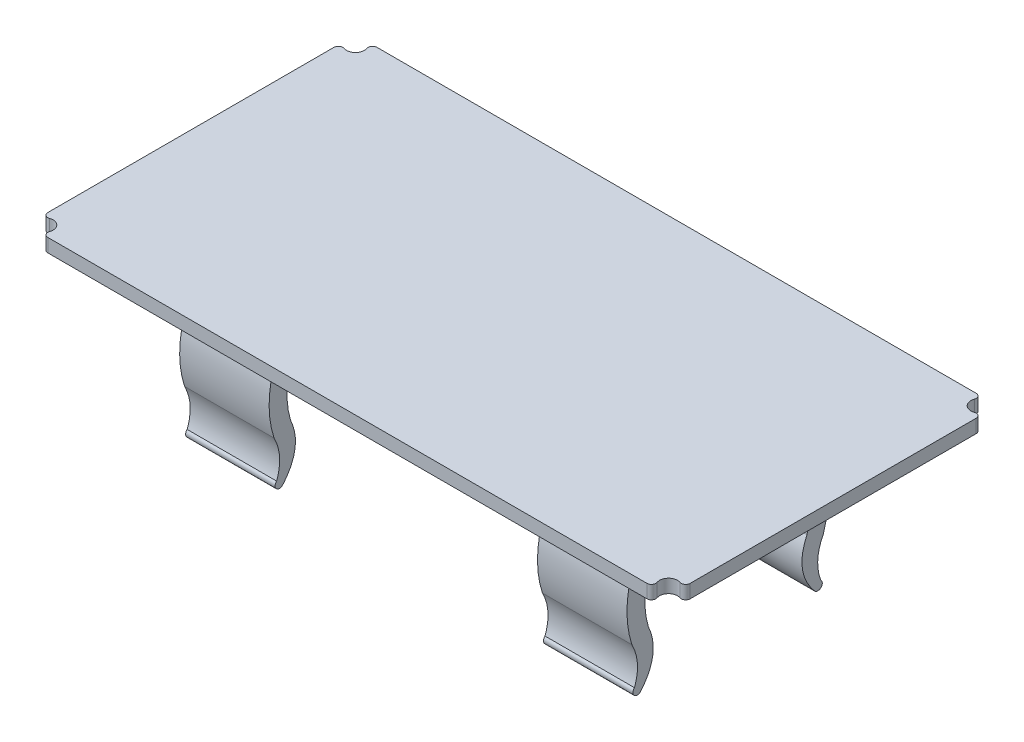
SolidWorks part; units mm, degrees
ref_plane "Front Plane" through (0, 0, 0) normal (0, 0, 1) x (1, 0, 0)
ref_plane "Top Plane" through (0, 0, 0) normal (0, 1, 0) x (1, 0, 0)
ref_plane "Right Plane" through (0, 0, 0) normal (1, 0, 0) x (0, 0, -1)
sketch "Sketch1" plane through (0, 0, 0) normal (0, 1, 0) x (1, 0, 0)
  line L1 (2.4142, 0) -> (69.3858, 0)
  line L2 (0, 2.4142) -> (0, 34.3858)
  line L3 (2.4142, 36.8) -> (69.3858, 36.8)
  line L4 (71.8, 2.4142) -> (71.8, 34.3858)
  arc A0 (0.6667, 34.8572) -> (1.9428, 36.1333) centre (1, 35.8) ccw
  arc A1 (1.9428, 0.6667) -> (0.6667, 1.9428) centre (1, 1) ccw
  arc A2 (71.1333, 1.9428) -> (69.8572, 0.6667) centre (70.8, 1) ccw
  arc A3 (69.8572, 36.1333) -> (71.1333, 34.8572) centre (70.8, 35.8) ccw
  arc A4 (69.8572, 36.1333) -> (69.3858, 36.8) centre (69.3858, 36.3) ccw
  arc A5 (71.8, 34.3858) -> (71.1333, 34.8572) centre (71.3, 34.3858) ccw
  arc A6 (71.1333, 1.9428) -> (71.8, 2.4142) centre (71.3, 2.4142) ccw
  arc A7 (69.8572, 0.6667) -> (69.3858, 0) centre (69.3858, 0.5) cw
  arc A8 (2.4142, 0) -> (1.9428, 0.6667) centre (2.4142, 0.5) cw
  arc A9 (0, 2.4142) -> (0.6667, 1.9428) centre (0.5, 2.4142) ccw
  arc A10 (2.4142, 36.8) -> (1.9428, 36.1333) centre (2.4142, 36.3) ccw
  arc A11 (0, 34.3858) -> (0.6667, 34.8572) centre (0.5, 34.3858) cw
  dimension "D3" = 1
  dimension "D7" = 1
  dimension "D2" = 0.5
  dimension "D4" = 1
  dimension "D5" = 1
  dimension "D6" = 1
  dimension "D8" = 1
  dimension "D9" = 1
  dimension "D10" = 1
extrude "Boss-Extrude1" add sketch "Sketch1" along normal blind 1.5
sketch "Sketch2" plane through (0, 0, 0) normal (0, -1, 0) x (1, 0, 0)
  line L0 (0, -18.4) -> (71.8, -18.4) construction
  line L1 (0, -34.3858) -> (0, -2.4142) construction
  line L2 (71.8, -2.4142) -> (71.8, -34.3858) construction
  line L3 (3, -12.6466) -> (68, -12.6466) construction
  dimension "D1" = 65
  dimension "D2" = 3
sketch "Sketch3" plane through (0, 0, 0) normal (-1, 0, 0) x (0, 0, 1)
  line L0 (-36.8, 1.5) -> (-36.8, 0) construction
  line L1 (-24.426, 0) -> (-12.374, 0)
  line L2 (-18.4, 0) -> (-18.4, -19) construction
  line L3 (-34.3858, 0) -> (-2.4142, 0) construction
  line L4 (-28.2071, -18.0824) -> (-8.5929, -18.0824) construction
  arc A0 (-24.426, 0) -> (-29.0982, -12.9801) centre (-18.4, -9.5) ccw
  arc A1 (-9.5316, -12.1294) -> (-27.2684, -12.1294) centre (-18.4, -9.5) ccw
  arc A2 (-28.8121, -17.2883) -> (-28.2071, -18.0824) centre (-28.4865, -17.6677) ccw
  circle A3 centre (-18.4, -9.5) radius 11.25 construction
  arc A5 (-7.9879, -17.2883) -> (-8.5929, -18.0824) centre (-8.3135, -17.6677) cw
  arc A8 (-7.7018, -12.9801) -> (-12.374, 0) centre (-18.4, -9.5) ccw
  circle A10 centre (-18.4, -9.5) radius 9.25 construction
  spline S0 degree 2 poles (-29.0982, -12.9801) (-28.0082, -15.0884) (-28.8121, -17.2883) knots 0 0 0 1 1 1
  spline S1 degree 2 poles (-27.2684, -12.1294) (-25.7983, -15.3459) (-28.2071, -18.0824) knots 0 0 0 1 1 1
  spline S2 degree 2 poles (-7.7018, -12.9801) (-8.7918, -15.0884) (-7.9879, -17.2883) knots 0 0 0 1 1 1
  spline S3 degree 2 poles (-9.5316, -12.1294) (-11.0017, -15.3459) (-8.5929, -18.0824) knots 0 0 0 1 1 1
  point P2 (-36.8, 0.75)
  point P5 (-18.4, -9.5)
  point P6 (-33.8544, -1.1798)
  point P7 (-32.928, 0)
  point P12 (-25.4426, -5.8774)
  point P13 (-7.4, -9.5)
  point P15 (-7.4, -9.5)
  point P20 (-26.369, -7.0572)
  point P23 (-9.3151, -6.7225)
  point P29 (-9.3151, -6.7225)
  line M1 (-34.3858, 0) -> (-2.4142, 0)
  dimension "D1" = 18.4
  dimension "D4" = 0.5
  dimension "D5" = 6.026
  dimension "D6" = 18.5
  dimension "D7" = 6.026
  dimension "D2" = 9.5
  dimension "D3" = 2
extrude "Boss-Extrude2" add sketch "Sketch3" against normal blind 10 from offset 10 contours M1 region at (0, -0.0289, -18.4) offset against normal yes
extrude "Boss-Extrude3" add sketch "Sketch3<3>" against normal blind 10 from offset 50 offset against normal yes
sketch "Sketch3<3>" plane through (0, 0, 0) normal (-1, 0, 0) x (0, 0, 1) same geometry as "Sketch3"
fillet "Fillet1" radius 2 4 edges at (55, 0, -24.426) (15, 0, -24.426) (55, 0, -12.374) (15, 0, -12.374)
